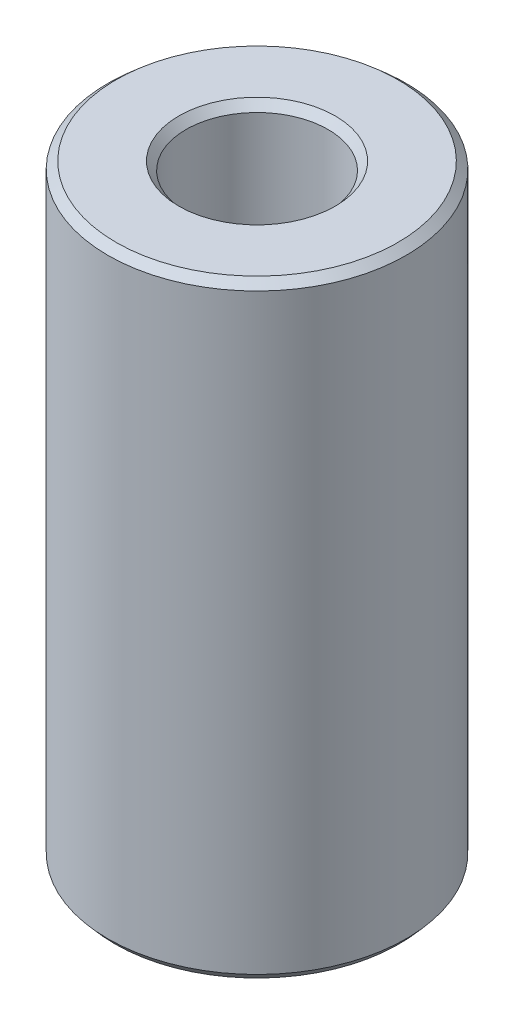
SolidWorks part; units mm, degrees
ref_plane "Front Plane" through (0, 0, 0) normal (0, 0, 1) x (1, 0, 0)
ref_plane "Top Plane" through (0, 0, 0) normal (0, 1, 0) x (1, 0, 0)
ref_plane "Right Plane" through (0, 0, 0) normal (1, 0, 0) x (0, 0, -1)
sketch "Sketch1" plane through (0, 0, 0) normal (0, 1, 0) x (1, 0, 0)
  circle A0 centre (0, 0) radius 5
  dimension "SLEEVE_OD" = 10
extrude "Boss-Extrude1" add sketch "Sketch1" along normal blind 20.3631
sketch "Sketch2" plane through (0, 0, 0) normal (0, 1, 0) x (1, 0, 0)
  circle A0 centre (0, 0) radius 2.3833
  dimension "BORE_D" = 4.7667
extrude "Cut-Extrude1" cut sketch "Sketch2" along normal through all
chamfer "Chamfer1" distance 0.2399 angle 48.746 4 edges at (0, 20.3631, 2.3833) (0, 0, 2.3833) (0, 0, 5) (0, 20.3631, 5) first distance on face at (0, 20.3631, 2.3833) first distance on face at (0, 0, 2.3833) first distance on face at (0, 20.3631, 5)
